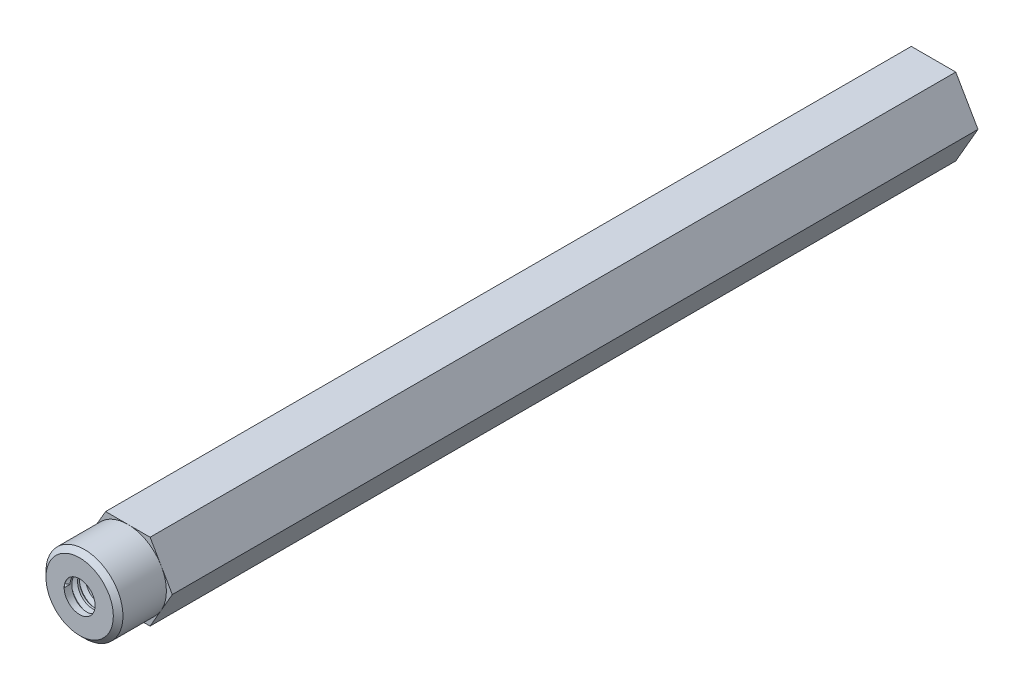
SolidWorks part; units mm, degrees
material "7075-T6 (SN)"
ref_plane "Alzado" through (0, 0, 0) normal (0, 0, 1) x (1, 0, 0)
ref_plane "Planta" through (0, 0, 0) normal (0, 1, 0) x (1, 0, 0)
ref_plane "Vista lateral" through (0, 0, 0) normal (1, 0, 0) x (0, 0, -1)
sketch "Croquis2" plane through (0, 0, 0) normal (0, 0, 1) x (1, 0, 0)
  line L1 (3.6662, -6.35) -> (7.3323, 0)
  line L2 (7.3323, 0) -> (3.6662, 6.35)
  line L3 (3.6662, 6.35) -> (-3.6662, 6.35)
  line L4 (-3.6662, 6.35) -> (-7.3323, 0)
  line L5 (-7.3323, 0) -> (-3.6662, -6.35)
  line L6 (-3.6662, -6.35) -> (3.6662, -6.35)
  circle A0 centre (0, 0) radius 6.35 construction
  dimension "D1" = 12.7
extrude "Extrusión Hex Profile" add sketch "Croquis2" along normal mid plane 140.7922
sketch "Croquis3" plane through (0, 0, 0) normal (0, 0, 1) x (1, 0, 0)
  circle A0 centre (0, 0) radius 2.5527
  dimension "D1" = 5.1054
extrude "Tap Hole 1" cut sketch "Croquis3" against normal blind 19.05 from surface starting at face at (0, 0, 70.3961)
extrude "Tap Hole 2" cut sketch "Croquis3<3>" along normal blind 19.05 from surface starting at face at (0, 0, -70.3961)
sketch "Croquis3<3>" plane through (0, 0, 0) normal (0, 0, 1) x (1, 0, 0) same geometry as "Croquis3"
sketch "Croquis7" plane through (0, 0, 0) normal (0, 0, 1) x (1, 0, 0)
  circle A0 centre (0, 0) radius 6.8707
  dimension "D1" = 13.7414
extrude "ThunderHex" [suppressed] cut sketch "Croquis7" against normal through all both and the other way through all flip side to cut
sketch "Croquis8" plane through (0, 0, 0) normal (0, 1, 0) x (1, 0, 0)
  line L0 (0, -70.3961) -> (-5.5562, -70.3961) construction
  line L1 (3.6662, -70.3961) -> (-3.6662, -70.3961) construction
  line L3 (0, -70.3961) -> (0, 0) construction
  line L4 (-5.5562, -70.3961) -> (-6.35, -69.6024)
  line L5 (-6.35, -69.6024) -> (-6.35, -68.8086)
  line L6 (-6.35, -68.8086) -> (-5.9055, -68.8086)
  line L7 (-5.9055, -68.8086) -> (-5.9055, -67.2211)
  line L8 (-5.9055, -67.2211) -> (-12.7, -67.2211)
  line L9 (-12.7, -67.2211) -> (-12.7, -70.3961)
  line L10 (-12.7, -70.3961) -> (-5.5562, -70.3961)
  line L11 (-3.6662, -70.3961) -> (-7.3323, -70.3961) construction
  dimension "D1" = 11.811
  dimension "D2" = 12.7
  dimension "D3" = 45
  dimension "D4" = 0.7937
  dimension "D6" = 0.7937
  dimension "D7" = 3.175
  dimension "D8" = 25.4
revolve "Retaining Ring 1" [suppressed] cut sketch "Croquis8" angle 360 about L3
sketch "Croquis9" plane through (0, 0, 0) normal (0, -1, 0) x (1, 0, 0)
  line L0 (0, -70.3961) -> (-5.5562, -70.3961) construction
  line L3 (0, -70.3961) -> (0, 0) construction
  line L4 (-5.5562, -70.3961) -> (-6.35, -69.6024)
  line L5 (-6.35, -69.6024) -> (-6.35, -68.8086)
  line L6 (-6.35, -68.8086) -> (-5.9055, -68.8086)
  line L7 (-5.9055, -68.8086) -> (-5.9055, -67.2211)
  line L8 (-5.9055, -67.2211) -> (-12.7, -67.2211)
  line L9 (-12.7, -67.2211) -> (-12.7, -70.3961)
  line L10 (-12.7, -70.3961) -> (-5.5562, -70.3961)
  line L12 (-3.6662, -70.3961) -> (3.6662, -70.3961) construction
  line L13 (-7.3323, -70.3961) -> (-3.6662, -70.3961) construction
  dimension "D1" = 11.811
  dimension "D2" = 12.7
  dimension "D3" = 45
  dimension "D4" = 0.7937
  dimension "D6" = 0.7937
  dimension "D7" = 3.175
  dimension "D8" = 25.4
revolve "Retaining Ring 2" [suppressed] cut sketch "Croquis9" angle 360 about L3
sketch "Croquis10" plane through (0, 0, 0) normal (0, 1, 0) x (1, 0, 0)
  line L0 (0, -70.3961) -> (0, 0) construction
  line L1 (3.6662, -70.3961) -> (-3.6662, -70.3961) construction
  line L2 (0, -70.3961) -> (-5.5562, -70.3961) construction
  line L3 (-3.6662, -70.3961) -> (-7.3323, -70.3961) construction
  line L4 (-5.5562, -70.3961) -> (-6.35, -69.6024)
  line L5 (-6.35, -69.6024) -> (-6.35, -62.4459)
  line L6 (-6.35, -62.4459) -> (-9.525, -62.4459)
  line L7 (-9.525, -62.4459) -> (-9.525, -70.3961)
  line L8 (-9.525, -70.3961) -> (-5.5562, -70.3961)
  dimension "D2" = 12.7
  dimension "D1" = 45
  dimension "D3" = 0.7937
  dimension "D4" = 7.9502
  dimension "D5" = 19.05
revolve "Round End 1" cut sketch "Croquis10" angle 360 about L0
sketch "Croquis12" plane through (0, 0, 0) normal (0, -1, 0) x (1, 0, 0)
  line L0 (0, -70.3961) -> (0, 0) construction
  line L2 (0, -70.3961) -> (-5.5562, -70.3961) construction
  line L4 (-5.5562, -70.3961) -> (-6.35, -69.6024)
  line L5 (-6.35, -69.6024) -> (-6.35, -62.4459)
  line L6 (-6.35, -62.4459) -> (-9.525, -62.4459)
  line L7 (-9.525, -62.4459) -> (-9.525, -70.3961)
  line L8 (-9.525, -70.3961) -> (-5.5562, -70.3961)
  line L9 (-3.6662, -70.3961) -> (3.6662, -70.3961) construction
  dimension "D1" = 45
  dimension "D3" = 0.7937
  dimension "D4" = 7.9502
  dimension "D2" = 12.7
  dimension "D5" = 19.05
revolve "Round End 2" [suppressed] cut sketch "Croquis12" angle 360 about L0
thread "Rosca1" pitch 1.27 method cut profile "Perfil de rosca1" start angle 0, offset 0, length 0, pitch 1.27, diameter 5.1054
ref_plane "Plano1" through (2.5527, 0, -70.3961) normal (0, -1, 0) x (1, 0, 0)
sketch "Perfil de rosca1" plane through (2.5527, 0, -70.3961) normal (0, -1, 0) x (1, 0, 0)
  line L0 (0, 0) -> (0, 1.27) construction
  line L1 (0, 0) -> (0.6874, 0.3969)
  line L2 (0.6874, 0.3969) -> (0.6874, 0.5556)
  line L3 (0.6874, 0.5556) -> (0, 0.9525)
  line L4 (0.6874, 0.4762) -> (0, 0.4762) construction
  line L11 (0, 0) -> (0, 0.9525)
  point P2 (0, 0)
  dimension "Pitch" = 1.27
  dimension "Profile_Angle" = 60
  dimension "Profile_Land" = 0.1588
  dimension "Profile_Height" = 0.6874
thread "Rosca2" pitch 1.27 method cut profile "Perfil de rosca2" start angle 0, offset 0, length 0, pitch 1.27, diameter 5.1054
ref_plane "Plano2" through (-2.5527, 0, 70.3961) normal (0, -1, 0) x (-1, 0, 0)
sketch "Perfil de rosca2" plane through (-2.5527, 0, 70.3961) normal (0, -1, 0) x (-1, 0, 0)
  line L0 (0, 0) -> (0, 1.27) construction
  line L1 (0, 0) -> (0.6874, 0.3969)
  line L2 (0.6874, 0.3969) -> (0.6874, 0.5556)
  line L3 (0.6874, 0.5556) -> (0, 0.9525)
  line L4 (0.6874, 0.4762) -> (0, 0.4762) construction
  line L11 (0, 0) -> (0, 0.9525)
  point P2 (0, 0)
  dimension "Pitch" = 1.27
  dimension "Profile_Angle" = 60
  dimension "Profile_Land" = 0.1588
  dimension "Profile_Height" = 0.6874
equation "\"HexOD\"= 0.5pulgadas"
equation "\"Largo\"= 5.543pulgadas"
equation "\"D1@Croquis2\"=\"HexOD\""
equation "\"D1@Extrusión Hex Profile\" = \"Largo\""
equation "\"TapHole\"= IIF ( \"HexOD\" = 0.5pulgadas , 0.2010pulgadas , 0.190pulgadas )"
equation "\"D1@Croquis3\"=\"TapHole\""
equation "\"ProTapHole\"= 0.75pulgadas"
equation "\"D1@Tap Hole 1\" = \"ProTapHole\""
equation "\"D1@Tap Hole 2\" = \"ProTapHole\""
equation "\"ThunderHex\"= IIF ( \"HexOD\" = 0.5pulgadas , 0.541pulgadas , 0.4035pulgadas )"
equation "\"D1@Croquis7\"=\"ThunderHex\""
equation "\"D2@Croquis8\"=\"HexOD\""
equation "\"D1@Croquis8\"=if(\"HexOD\"=0.5pulgadas, 0.465pulgadas, 0.35pulgadas )"
equation "\"D2@Croquis9\"=\"HexOD\""
equation "\"D1@Croquis9\"=if(\"HexOD\"=0.5pulgadas, 0.465pulgadas, 0.35pulgadas )"
equation "\"D8@Croquis8\"=\"HexOD\"*2"
equation "\"D8@Croquis9\"=\"HexOD\"*2"
equation "\"D5@Croquis10\"=\"HexOD\"*1.5"
equation "\"D5@Croquis12\"=\"HexOD\"*1.5"
equation "\"D4@Croquis10\"=if( \"D2@Croquis10\"=<0.375, 0.28, 0.313)"
equation "\"D4@Croquis12\"=if( \"D2@Croquis10\"=<0.375, 0.28, 0.313)"
